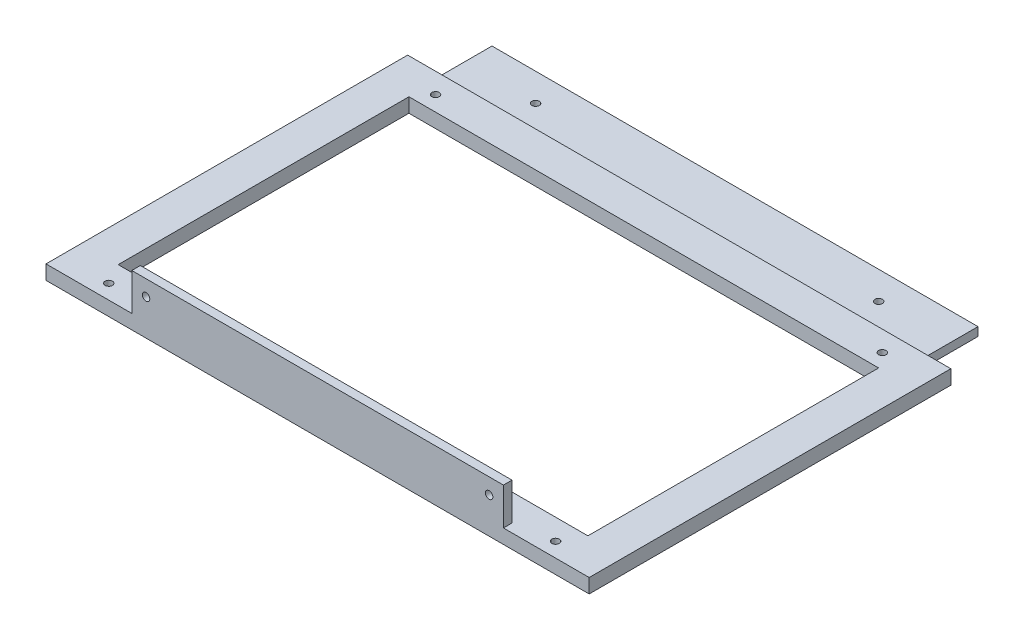
SolidWorks part; units mm, degrees
ref_plane "Front Plane" through (0, 0, 0) normal (0, 0, 1) x (1, 0, 0)
ref_plane "Top Plane" through (0, 0, 0) normal (0, 1, 0) x (1, 0, 0)
ref_plane "Right Plane" through (0, 0, 0) normal (1, 0, 0) x (0, 0, -1)
sketch "Sketch1" plane through (0, 0, 0) normal (0, 1, 0) x (1, 0, 0)
  line L1 (-85, 73) -> (85, 73)
  line L2 (-85, 73) -> (-85, -73)
  line L3 (-85, -73) -> (85, -73)
  line L4 (85, 73) -> (85, -73)
  line L5 (-85, 73) -> (85, -73) construction
  line L6 (-85, -73) -> (85, 73) construction
  point P0 (0, 0)
  dimension "D1" = 170
  dimension "D2" = 146
extrude "Boss-Extrude1" add sketch "Sketch1" along normal blind 3
sketch "Sketch2" plane through (0, 3, 0) normal (0, 1, 0) x (1, 0, 0)
  line L0 (0, 73) -> (0, 46.4)
  line L3 (85, 73) -> (-85, 73) construction
  circle A0 centre (-78.15, 46.4) radius 1.3
  circle A2 centre (78.15, 46.4) radius 1.3
  circle A3 centre (-78.15, -67.9) radius 1.3
  circle A4 centre (78.15, -67.9) radius 1.3
extrude "Cut-Extrude1" cut sketch "Sketch2" against normal blind 3 contours A4 | A0 | A3 | A2 region at (78.15, 3, 67.9)
sketch "Sketch3" plane through (0, 3, 0) normal (0, 1, 0) x (1, 0, 0)
  line L0 (-78.15, 45.1) -> (-78.15, 41.1)
  line L1 (-78.15, -66.6) -> (-78.15, -60.6)
  line L2 (78.15, -66.6) -> (78.15, -60.6)
  line L3 (78.15, 45.1) -> (78.15, 41.1)
  line L4 (-78.15, 41.1) -> (-82.15, 41.1)
  line L5 (-78.15, -60.6) -> (-82.15, -60.6)
  line L6 (-82.15, -60.6) -> (-82.15, 41.1)
  line L7 (78.15, 41.1) -> (82.15, 41.1)
  line L8 (82.15, 41.1) -> (82.15, -60.6)
  line L9 (82.15, -60.6) -> (78.15, -60.6)
  line L10 (-78.15, 41.1) -> (78.15, 41.1)
  line L11 (-78.15, -60.6) -> (78.15, -60.6)
  circle A0 centre (-78.15, 46.4) radius 1.3 construction
  circle A1 centre (-78.15, -67.9) radius 1.3 construction
  circle A2 centre (78.15, -67.9) radius 1.3 construction
  circle A3 centre (78.15, 46.4) radius 1.3 construction
extrude "Cut-Extrude2" cut sketch "Sketch3" against normal blind 3 contours L5 L11 L9 L8 L7 L10 L4 L6 region at (0, 3, 9.75)
sketch "Sketch4" plane through (0, 3, 0) normal (0, 1, 0) x (1, 0, 0)
  line L1 (-82.15, 53.5) -> (85, 53.5)
  line L2 (85, -73) -> (85, 73) construction
  line L3 (85, 53.5) -> (85, -73)
  line L4 (85, -73) -> (-85, -73)
  line L5 (-85, -73) -> (-85, 53.5)
  line L6 (-85, 73) -> (-85, -73) construction
  line L7 (-85, 53.5) -> (-82.15, 53.5)
  line L8 (-82.15, 41.1) -> (82.15, 41.1)
  line L9 (-82.15, 41.1) -> (-82.15, -60.6)
  line L10 (-82.15, -60.6) -> (82.15, -60.6)
  line L11 (82.15, 41.1) -> (82.15, -60.6)
  circle A0 centre (-78.15, 46.4) radius 1.3
  circle A1 centre (-78.15, -67.9) radius 1.3
  circle A2 centre (78.15, -67.9) radius 1.3
  circle A3 centre (78.15, 46.4) radius 1.3
extrude "Boss-Extrude2" add sketch "Sketch4" along normal blind 2
sketch "Sketch9" plane through (-85, 0, 0) normal (-1, 0, 0) x (0, 0, 1)
  line L0 (-53.5, 3) -> (-53.5, 5)
  line L1 (-53.5, 5) -> (73, 5)
  line L2 (73, 5) -> (73, 0)
  line L3 (73, 0) -> (-53.5, 0)
  line L4 (-73, 0) -> (73, 0) construction
  line L5 (-53.5, 0) -> (-53.5, 3)
extrude "Boss-Extrude5" add sketch "Sketch9" along normal blind 10
sketch "Sketch10" plane through (85, 0, 0) normal (1, 0, 0) x (0, 0, -1)
  line L0 (-73, 5) -> (-73, 0)
  line L1 (-73, 0) -> (53.5, 0)
  line L2 (53.5, 0) -> (53.5, 5)
  line L3 (53.5, 5) -> (-73, 5)
extrude "Boss-Extrude6" add sketch "Sketch10" along normal blind 10
sketch "Sketch12" plane through (0, 5, 0) normal (0, 1, 0) x (1, 0, 0)
  line L0 (-95, -73) -> (-95, -70)
  line L1 (-95, -73) -> (-95, 53.5) construction
  line L2 (-95, -70) -> (95, -70)
  line L3 (95, 53.5) -> (95, -73) construction
  line L4 (95, -70) -> (95, -73)
  line L5 (95, -73) -> (-95, -73)
extrude "Boss-Extrude8" add sketch "Sketch12" along normal blind 13
sketch "Sketch13" plane through (0, 3, 0) normal (0, 1, 0) x (1, 0, 0)
  circle A0 centre (-60, 63.25) radius 1.3
  circle A1 centre (60, 63.25) radius 1.3
extrude "Cut-Extrude3" cut sketch "Sketch13" against normal blind 13
fillet "Fillet4" radius 2 1 edges at (0, 3, -53.5)
sketch "Sketch14" plane through (0, 0, 70) normal (0, 0, -1) x (-1, 0, 0)
  circle A0 centre (-60, 12.5) radius 1.3
  circle A1 centre (60, 12.5) radius 1.3
extrude "Cut-Extrude4" cut sketch "Sketch14" against normal blind 13
sketch "Sketch15" plane through (0, 18, 0) normal (0, 1, 0) x (1, 0, 0)
  line L0 (95, -70) -> (65, -70)
  line L1 (95, -70) -> (-95, -70) construction
  line L2 (65, -70) -> (65, -73)
  line L3 (-95, -73) -> (95, -73) construction
  line L4 (65, -73) -> (95, -73)
  line L5 (95, -73) -> (95, -70)
  line L6 (-95, -70) -> (-65, -70)
  line L7 (-65, -70) -> (-65, -73)
  line L8 (-65, -73) -> (-95, -73)
  line L9 (-95, -73) -> (-95, -70)
extrude "Cut-Extrude5" cut sketch "Sketch15" against normal up to surface (13 mm away) up to face at (0, 5, 9.75)
